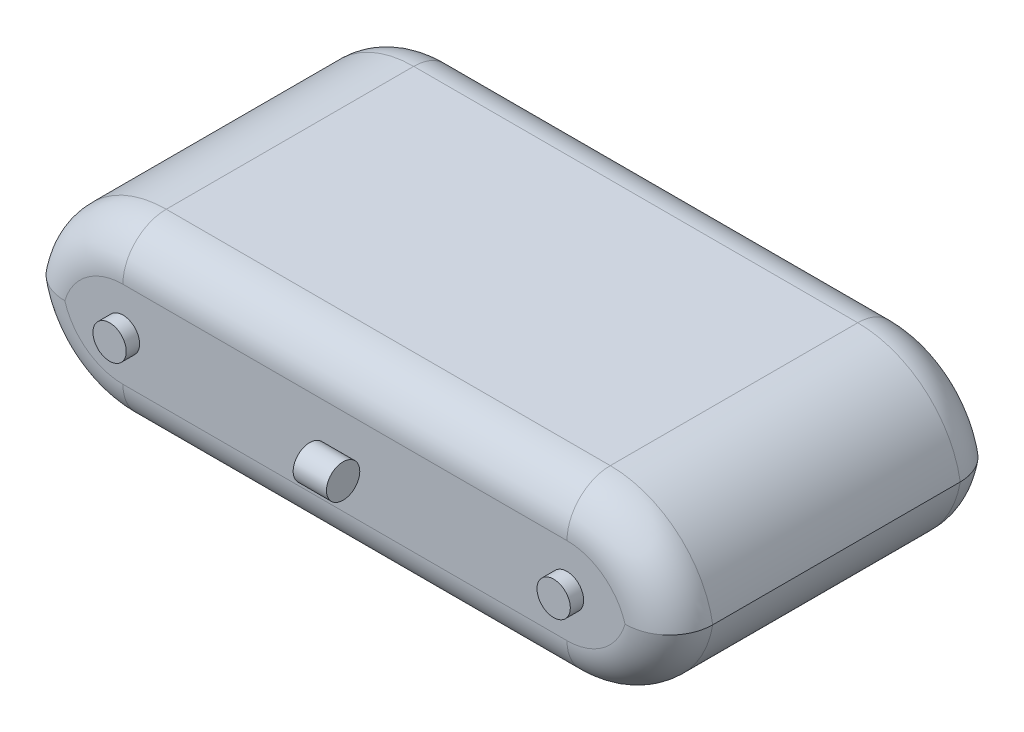
SolidWorks part; units mm, degrees
ref_plane "Front Plane" through (0, 0, 0) normal (0, 0, 1) x (1, 0, 0)
ref_plane "Top Plane" through (0, 0, 0) normal (0, 1, 0) x (1, 0, 0)
ref_plane "Right Plane" through (0, 0, 0) normal (1, 0, 0) x (0, 0, -1)
sketch "Sketch1" plane through (0, 0, 0) normal (0, 1, 0) x (1, 0, 0)
  line L1 (-35.3566, 17.0087) -> (39.9101, 17.0087)
  line L2 (-35.3566, 17.0087) -> (-35.3566, -21.5622)
  line L3 (-35.3566, -21.5622) -> (39.9101, -21.5622)
  line L4 (39.9101, 17.0087) -> (39.9101, -21.5622)
extrude "Boss-Extrude1" add sketch "Sketch1" along normal blind 20
fillet "Fillet1" radius 12 4 edges at (39.9101, 20, 2.2768) (39.9101, 0, 2.2768) (-35.3566, 0, 2.2768) (-35.3566, 20, 2.2768)
fillet "Fillet3" radius 5 12 edges at (35.6561, 2.8348, 21.5622) (35.6561, 17.1652, 21.5622) (2.2768, 0, 21.5622) (2.2768, 20, 21.5622) (-31.1026, 2.8348, 21.5622) (-31.1026, 17.1652, 21.5622) (35.6561, 17.1652, -17.0087) (35.6561, 2.8348, -17.0087) (-31.1026, 17.1652, -17.0087) (-31.1026, 2.8348, -17.0087) (2.2768, 0, -17.0087) (2.2768, 20, -17.0087)
scale "Scale1" scale about centroid uniform scaling yes scale factor 13
sketch "Sketch2" plane through (0, 0, 252.9872) normal (0, 0, 1) x (1, 0, 0)
  circle A1 centre (-330.9568, 10) radius 25
  circle A2 centre (335.5103, 10) radius 25
extrude "Boss-Extrude2" add sketch "Sketch2" along normal blind 20 contours A1 | A2
sketch "Sketch3" plane through (0, 0, -248.4337) normal (0, 0, -1) x (-1, 0, 0)
  circle A1 centre (-335.5103, 10) radius 25
  circle A2 centre (330.9568, 10) radius 25
extrude "Boss-Extrude3" add sketch "Sketch3" along normal blind 20
sketch "Sketch4" plane through (0, 0, 252.9872) normal (0, 0, 1) x (1, 0, 0)
  circle A0 centre (-36.5099, 10) radius 20
  circle A1 centre (43.4568, 10) radius 20
extrude "Boss-Extrude4" [suppressed] add sketch "Sketch4" along normal blind 20
sketch "Sketch6" plane through (0, 0, 0) normal (1, 0, 0) x (0, 0, -1)
  circle A0 centre (-278.4644, 10) radius 25
  circle A1 centre (273.852, 10) radius 25
  point P2 (273.852, 10)
extrude "Boss-Extrude5" add sketch "Sketch6" along normal mid plane 50 separate body
